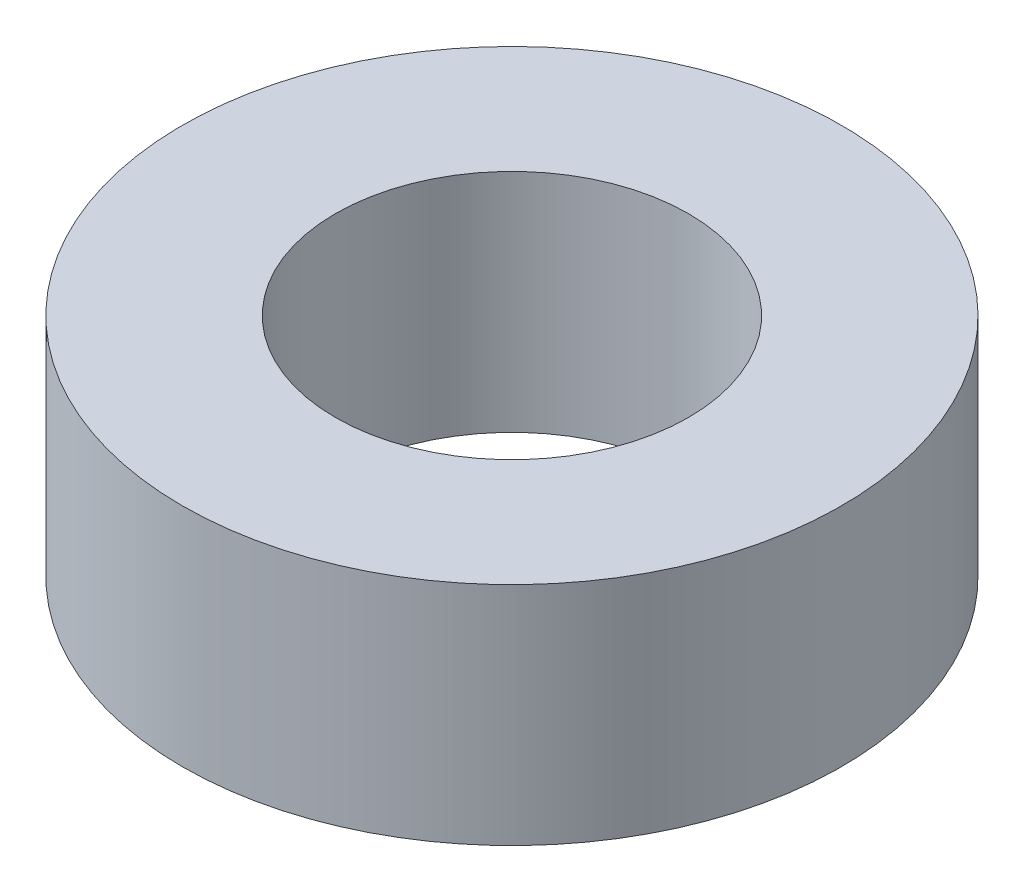
SolidWorks part; units mm, degrees
ref_plane "Front Plane" through (0, 0, 0) normal (0, 0, 1) x (1, 0, 0)
ref_plane "Top Plane" through (0, 0, 0) normal (0, 1, 0) x (1, 0, 0)
ref_plane "Right Plane" through (0, 0, 0) normal (1, 0, 0) x (0, 0, -1)
ref_plane "Plane1"
sketch "Sketch1" plane through (0, 0, 0) normal (0, 1, 0) x (-1, 0, 0)
  circle A0 centre (0, 0) radius 7
  circle A1 centre (0, 0) radius 3.75
  dimension "D1" = 7.5
  dimension "D2" = 14
extrude "Extrusion1" add sketch "Sketch1" along normal blind 4.8 contours A0 A1 region at (6.802, 0, 0)
